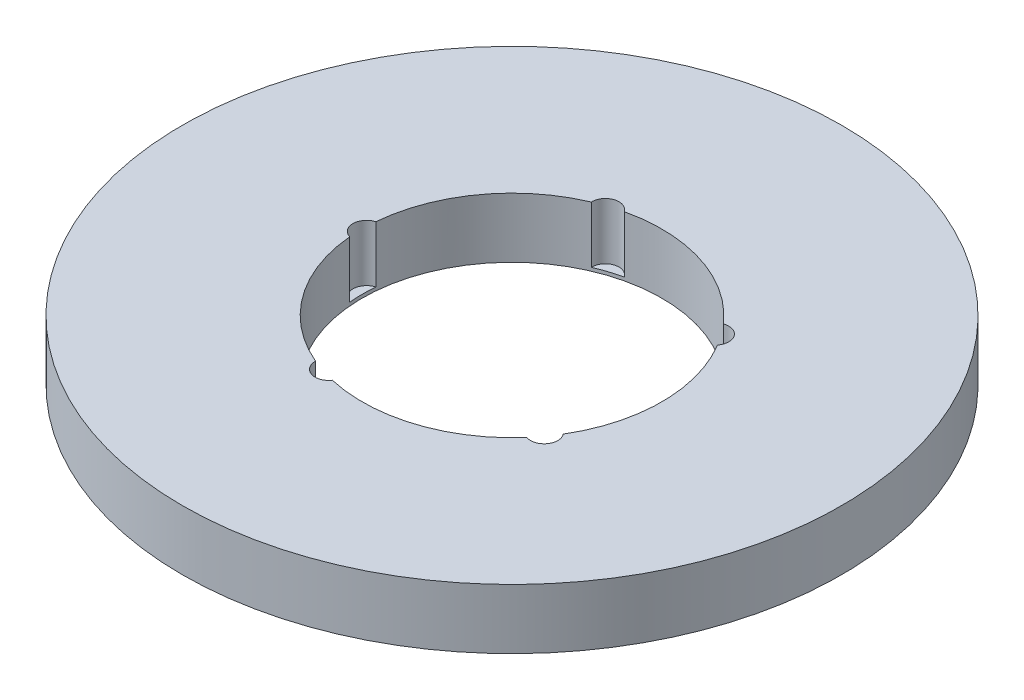
SolidWorks part; units mm, degrees
ref_plane "Front Plane" through (0, 0, 0) normal (0, 0, 1) x (1, 0, 0)
ref_plane "Top Plane" through (0, 0, 0) normal (0, 1, 0) x (1, 0, 0)
ref_plane "Right Plane" through (0, 0, 0) normal (1, 0, 0) x (0, 0, -1)
sketch "Sketch1" plane through (0, 0, 0) normal (0, 1, 0) x (1, 0, 0)
  circle A0 centre (0, 0) radius 55
  dimension "FLANGE_OD" = 110
extrude "Boss-Extrude1" add sketch "Sketch1" along normal blind 10
sketch "Sketch2" plane through (0, 0, 0) normal (0, 1, 0) x (1, 0, 0)
  circle A0 centre (0, 0) radius 25
  dimension "BORE_D" = 50
extrude "Cut-Extrude1" cut sketch "Sketch2" along normal through all
sketch "Sketch3" plane through (0, 10, 0) normal (0, 1, 0) x (1, 0, 0)
  circle A0 centre (0, 0) radius 24.2756 construction
  circle A1 centre (-24.2756, 0) radius 2.2705
  dimension "BOLT_D" = 4.5409
  dimension "BOLT_PCD" = 48.5512
extrude "Cut-Extrude2" cut sketch "Sketch3" against normal blind 9.4397
pattern_circular "CirPattern1" count 5 over 360 about axis through (0, 0, 0) along (0, 1, 0) of "Cut-Extrude2"
